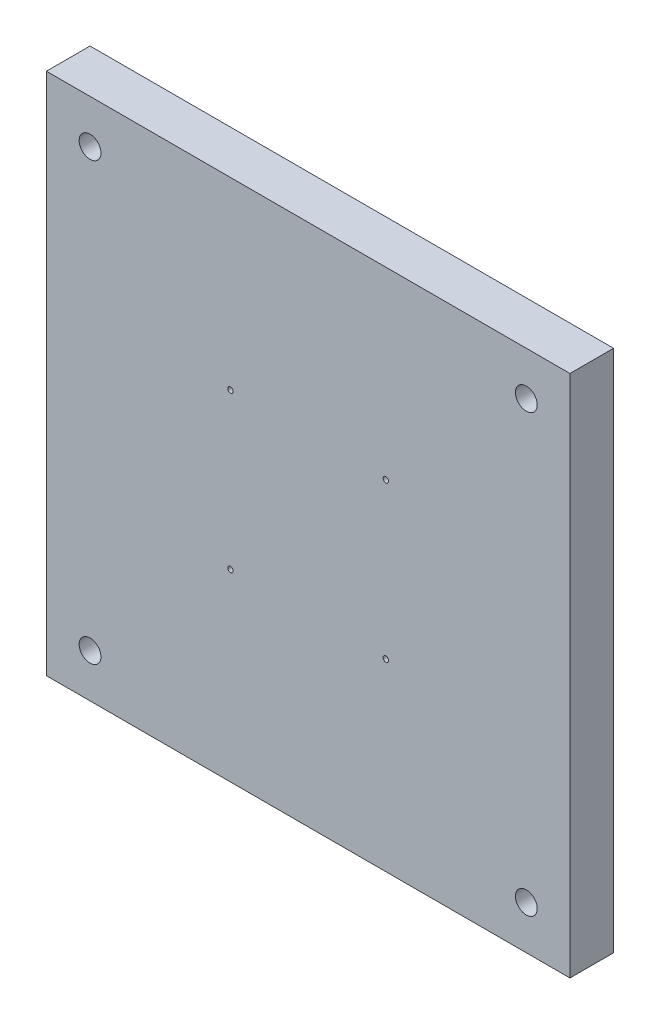
SolidWorks part; units mm, degrees
ref_plane "Front Plane" through (0, 0, 0) normal (0, 0, 1) x (1, 0, 0)
ref_plane "Top Plane" through (0, 0, 0) normal (0, 1, 0) x (1, 0, 0)
ref_plane "Right Plane" through (0, 0, 0) normal (1, 0, 0) x (0, 0, -1)
sketch "Sketch1" plane through (0, 0, 0) normal (0, 0, 1) x (1, 0, 0)
  line L1 (0, 0) -> (76.2, 0)
  line L2 (0, 0) -> (0, 76.2)
  line L3 (0, 76.2) -> (76.2, 76.2)
  line L4 (76.2, 0) -> (76.2, 76.2)
  dimension "D1" = 76.2
  dimension "D2" = 76.2
extrude "Boss-Extrude1" add sketch "Sketch1" along normal blind 6.35
sketch3d "3DSketch1"
  circle A0 centre (49.403, 49.403, 52.578) radius 1.905 construction
  circle A1 centre (26.797, 49.403, 52.578) radius 1.905 construction
  circle A2 centre (26.797, 26.797, 52.578) radius 1.905 construction
  circle A3 centre (49.403, 26.797, 52.578) radius 1.905 construction
  circle A4 centre (49.403, 49.403, 52.578) radius 1.905
  circle A5 centre (26.797, 49.403, 52.578) radius 1.905
  circle A6 centre (26.797, 26.797, 52.578) radius 1.905
  circle A7 centre (49.403, 26.797, 52.578) radius 1.905
  point P2 (49.403, 49.403, 54.483)
  point P5 (26.797, 49.403, 54.483)
  point P8 (26.797, 26.797, 54.483)
  point P11 (49.403, 26.797, 54.483)
  point P13 (49.403, 49.403, 54.483)
  point P15 (26.797, 49.403, 54.483)
  point P17 (26.797, 26.797, 54.483)
  point P19 (49.403, 26.797, 54.483)
ref_axis "Axis1" through (0, 0, -2.6289) along (0, 0, 1)
sketch "Sketch3" plane through (0, 0, 6.35) normal (0, 0, 1) x (1, 0, 0)
  circle A0 centre (49.403, 49.403) radius 1.905 construction
  circle A1 centre (49.403, 26.797) radius 1.905 construction
  circle A2 centre (26.797, 49.403) radius 1.905 construction
  circle A3 centre (26.797, 26.797) radius 1.905 construction
  circle A4 centre (49.403, 49.403) radius 1.905 construction
  circle A5 centre (49.403, 26.797) radius 1.905 construction
  circle A6 centre (26.797, 49.403) radius 1.905 construction
  circle A7 centre (26.797, 26.797) radius 1.905 construction
  circle A8 centre (49.403, 49.403) radius 0.3969
  circle A9 centre (26.797, 49.403) radius 0.3969
  circle A10 centre (26.797, 26.797) radius 0.3969
  circle A11 centre (49.403, 26.797) radius 0.3969
  dimension "D1" = 0.7937
  dimension "D2" = 0.7937
  dimension "D3" = 0.7937
  dimension "D4" = 0.7937
extrude "Cut-Extrude2" cut sketch "Sketch3" against normal through all
sketch "Sketch4" plane through (0, 0, 0) normal (0, 0, -1) x (-1, 0, 0)
  line L0 (-6.35, 76.2) -> (-6.35, 69.85) construction
  line L1 (-76.2, 76.2) -> (0, 76.2) construction
  line L2 (-6.35, 69.85) -> (0, 69.85) construction
  line L3 (0, 76.2) -> (0, 0) construction
  line L4 (-76.2, 38.1) -> (0, 38.1) construction
  line L5 (-76.2, 0) -> (-76.2, 76.2) construction
  line L6 (-38.1, 0) -> (-38.1, 76.2) construction
  line L7 (0, 0) -> (-76.2, 0) construction
  circle A0 centre (-6.35, 69.85) radius 1.5875
  circle A1 centre (-6.35, 6.35) radius 1.5875
  circle A2 centre (-69.85, 69.85) radius 1.5875
  circle A3 centre (-69.85, 6.35) radius 1.5875
  dimension "D3" = 3.175
  dimension "D1" = 6.35
  dimension "D2" = 6.35
extrude "Cut-Extrude3" cut sketch "Sketch4" against normal through all
